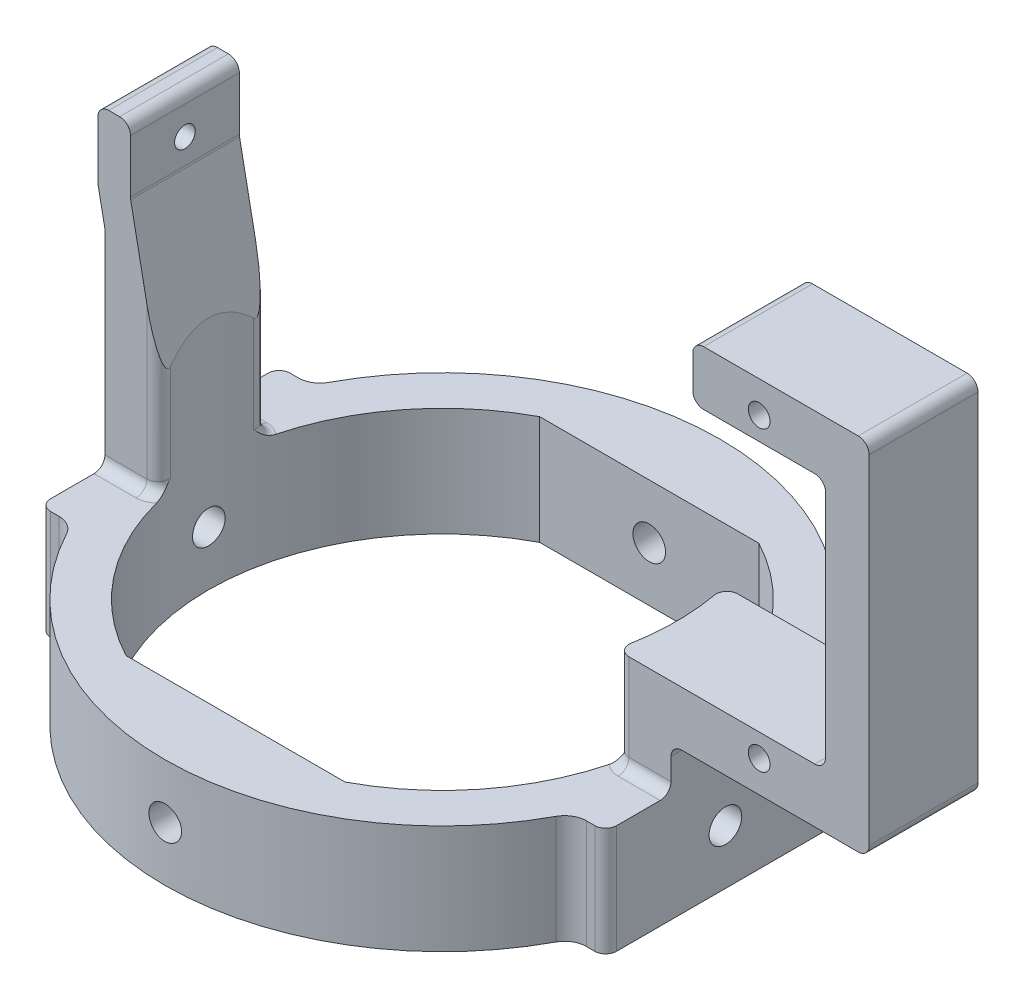
SolidWorks part; units mm, degrees
ref_plane "Front Plane" through (0, 0, 0) normal (0, 0, 1) x (1, 0, 0)
ref_plane "Top Plane" through (0, 0, 0) normal (0, 1, 0) x (1, 0, 0)
ref_plane "Right Plane" through (0, 0, 0) normal (1, 0, 0) x (0, 0, -1)
sketch "Sketch1" plane through (0, 0, 0) normal (0, 1, 0) x (1, 0, 0)
  line L0 (0, 0) -> (0, -50000) construction
  line L1 (-0.6553, 0) -> (-50000.6553, 0) construction
  line L2 (14.975, -4) -> (18.5, -4) construction
  line L3 (18.5, -4) -> (18.5, 4) construction
  line L4 (14.975, 4) -> (18.5, 4) construction
  line L5 (15.5, 0) -> (15.5, -50000) construction
  line L6 (19, -10.0623) -> (19, 10.0623)
  line L8 (-10.0623, -19) -> (10.0623, -19)
  line L9 (-19, 10.0623) -> (-19, -10.0623)
  line L10 (10.0623, 19) -> (-10.0623, 19)
  circle A0 centre (0, 0) radius 15.5 construction
  arc A1 (19, 10.0623) -> (10.0623, 19) centre (0, 0) ccw
  circle A2 centre (0, 0) radius 25.5
  arc A3 (-19, -10.0623) -> (-10.0623, -19) centre (0, 0) ccw
  arc A4 (10.0623, -19) -> (19, -10.0623) centre (0, 0) ccw
  arc A5 (-10.0623, 19) -> (-19, 10.0623) centre (0, 0) ccw
  point P13 (18.5, 0)
  point P27 (0, 0)
  dimension "D1" = 31
  dimension "D2" = 6
  dimension "D3" = 43
  dimension "D4" = 4
  dimension "D5" = 51
  dimension "D6" = 8
  dimension "D7" = 3
  dimension "D8" = 0.5
extrude "Ring" add sketch "Sketch1" along normal blind 10
sketch "Sketch2" plane through (0, 10, 0) normal (0, 1, 0) x (1, 0, 0)
  line L0 (0, -1000) -> (0, -26.5) construction
  line L1 (-1000, 0) -> (0, 0) construction
  line L2 (-23.0054, 11) -> (-26, 11)
  line L3 (-26, 11) -> (-26, -11)
  line L4 (-23.0054, -11) -> (-26, -11)
  line L5 (-25.5, 0) -> (-25.5, 50000) construction
  line L6 (23.0054, -11) -> (26, -11)
  line L7 (26, 11) -> (26, -11)
  line L8 (23.0054, 11) -> (26, 11)
  line L9 (0, 26.5) -> (0, 50000) construction
  line L10 (25.5, 0) -> (50000, 0) construction
  circle A0 centre (0, 0) radius 25.5 construction
  arc A1 (-23.0054, 11) -> (-23.0054, -11) centre (0, 0) ccw
  arc A2 (23.0054, -11) -> (23.0054, 11) centre (0, 0) ccw
  point P13 (-26, 0)
  point P15 (-25.5, 0)
  dimension "D1" = 22
  dimension "D2" = 0.5
extrude "Ring-Extensions" add sketch "Sketch2" against normal through all
ref_plane "MidPlane" through (0, 0, 0) normal (0, 0, 1) x (1, 0, 0)
ref_plane "ServoMountPlane" through (0, 0, 0) normal (0, 0, 1) x (1, 0, 0)
sketch "Sketch4" plane through (0, 0, 0) normal (0, 0, 1) x (1, 0, 0)
  line L0 (0, 0) -> (-20, 0) construction
  line L1 (-23.0054, 0) -> (23.0054, 0) construction
  line L2 (-20, -1000) -> (-20, 10) construction
  line L10 (23.0054, 10) -> (-23.0054, 10) construction
  line L11 (-26, 10) -> (-20, 10)
  line L17 (-20, 10) -> (-20, 14)
  line L18 (-20, 14) -> (-23.65, 32.571)
  line L19 (-23.65, 32.571) -> (-23.65, 38.571)
  line L20 (-23.65, 38.571) -> (-26.65, 38.571)
  line L21 (-26.65, 38.571) -> (-26.65, 32.279)
  line L22 (-26.65, 32.279) -> (-26, 28.9718)
  line L23 (-26, 28.9718) -> (-26, 10)
  line L24 (-29, 35.425) -> (-26.65, 35.425) construction
  line L25 (0, 0) -> (0, 50000) construction
  dimension "D1" = 20
  dimension "D2" = 26.65
  dimension "D3" = 4
  dimension "D4" = 3
  dimension "D5" = 3
  dimension "D6" = 6
  dimension "D7" = 25.425
extrude "Outer_Ring_Pushrod_mount" add sketch "Sketch4" along normal mid plane 10
sketch "Sketch5" plane through (0, 0, 0) normal (0, 0, 1) x (1, 0, 0)
  line L0 (0, 0) -> (0, 50000) construction
  line L1 (20, 0) -> (20, 50000) construction
  line L2 (20, 10) -> (20, 19)
  line L3 (26, 10) -> (20, 10)
  line L4 (23.0054, 10) -> (-23.0054, 10) construction
  line L5 (20, 19) -> (40.2, 19)
  line L6 (40.2, 19) -> (40.2, 42.1)
  line L7 (40.2, 42.1) -> (28, 42.1)
  line L8 (28, 42.1) -> (28, 47.1)
  line L9 (28, 47.1) -> (44.2, 47.1)
  line L10 (44.2, 47.1) -> (44.2, 14)
  line L11 (44.2, 14) -> (26, 14)
  line L12 (26, 14) -> (26, 10)
  line L13 (34.1, 42.25) -> (34.1, 50042.25) construction
  line L14 (35, 30.55) -> (50035, 30.55) construction
  circle A0 centre (34.1, 44.2) radius 1
  circle A1 centre (34.1, 16.9) radius 1
  point P20 (34.1, 42.1)
  point P25 (40.2, 30.55)
  dimension "D9" = 2
  dimension "D1" = 20
  dimension "D2" = 9
  dimension "D3" = 5
  dimension "D4" = 4
  dimension "D5" = 5
  dimension "D6" = 23.1
  dimension "D7" = 12.2
  dimension "D8" = 44.2
  dimension "D10" = 2.1
extrude "Servo_Mount" add sketch "Sketch5" along normal mid plane 10
sketch "Sketch6" plane through (0, 0, 0) normal (0, 0, 1) x (1, 0, 0)
  line L0 (10.0346, 10) -> (50010.0346, 10) construction
  line L1 (0, 0) -> (0, 10) construction
  line L2 (6.326, 0) -> (50006.326, 0) construction
  circle A0 centre (0, 5) radius 1.5
  dimension "D1" = 3
extrude "Motor_Mount_Holes" cut sketch "Sketch6" against normal mid plane 100
sketch "Sketch7" plane through (0, 10, 0) normal (0, 1, 0) x (1, 0, 0)
  line L2 (10.0623, 19) -> (-10.0623, 19) construction
  line L3 (-10.0623, -19) -> (10.0623, -19) construction
  line L4 (10.0623, 19) -> (-10.0623, 19)
  line L5 (-10.0623, -19) -> (10.0623, -19)
  arc A0 (10.0623, -19) -> (10.0623, 19) centre (0, 0) ccw
  arc A1 (-10.0623, 19) -> (-10.0623, -19) centre (0, 0) ccw
extrude "Cut-Extrude3" cut sketch "Sketch7" against normal mid plane 100
fillet "Fillet2" radius 1 16 edges at (20.9105, 14.5, -5) (20.9105, 14.5, 5) (26, 14, 0) (-26, 28.9718, 0) (-26.65, 32.279, 0) (-26.65, 38.571, 0) (-23.65, 38.571, 0) (-23.65, 32.571, 0) (40.2, 42.1, 0) (40.2, 19, 0) (44.2, 14, 0) (44.2, 47.1, 0) (28, 42.1, 0) (28, 47.1, 0) (-20.9105, 14.3163, -5) (-20.9105, 14.3163, 5)
fillet "Fillet3" radius 2 4 edges at (23.0054, 5, -11) (23.0054, 5, 11) (-23.0054, 5, -11) (-23.0054, 5, 11)
fillet "Fillet4" radius 1 8 edges at (24.0708, 10, -5) (24.0708, 10, 5) (-21.3742, 10, -4.6412) (21.3742, 10, -4.6412) (21.3742, 10, 4.6412) (-21.3742, 10, 4.6412) (-24.0708, 10, -5) (-24.0708, 10, 5)
fillet "Fillet5" radius 1 4 edges at (-26, 5, -11) (-26, 5, 11) (26, 5, 11) (26, 5, -11)
sketch "Sketch8" plane through (-26, 0, 0) normal (-1, 0, 0) x (0, 0, 1)
  line L0 (10, 10) -> (10, 0) construction
  line L1 (10, 0) -> (-10, 0) construction
  line L2 (-10, 0) -> (-10, 10) construction
  line L3 (-10, 10) -> (10, 10) construction
  line L4 (0, 0) -> (0, 10) construction
  line L6 (-10, 5) -> (10, 5) construction
  circle A0 centre (0, 5) radius 1.5
  dimension "D1" = 3
extrude "Outer-Ring-Mount-holes" cut sketch "Sketch8" against normal through all
sketch "Sketch9" plane through (-26.65, 0, 0) normal (-1, 0, 0) x (0, 0, 1)
  line L0 (5, 37.571) -> (-5, 37.571) construction
  line L1 (-5, 37.571) -> (-5, 32.3763) construction
  line L2 (-5, 32.3763) -> (5, 32.3763) construction
  line L3 (5, 32.3763) -> (5, 37.571) construction
  line L4 (0, 37.571) -> (0, 32.3763) construction
  line L5 (5, 34.9737) -> (-5, 34.9737) construction
  circle A0 centre (0, 34.9737) radius 0.95
  dimension "D1" = 1.9
extrude "Cut-Extrude5" cut sketch "Sketch9" against normal up to surface (3 mm away) up to face at (-23.65, 35.1197, 0)
